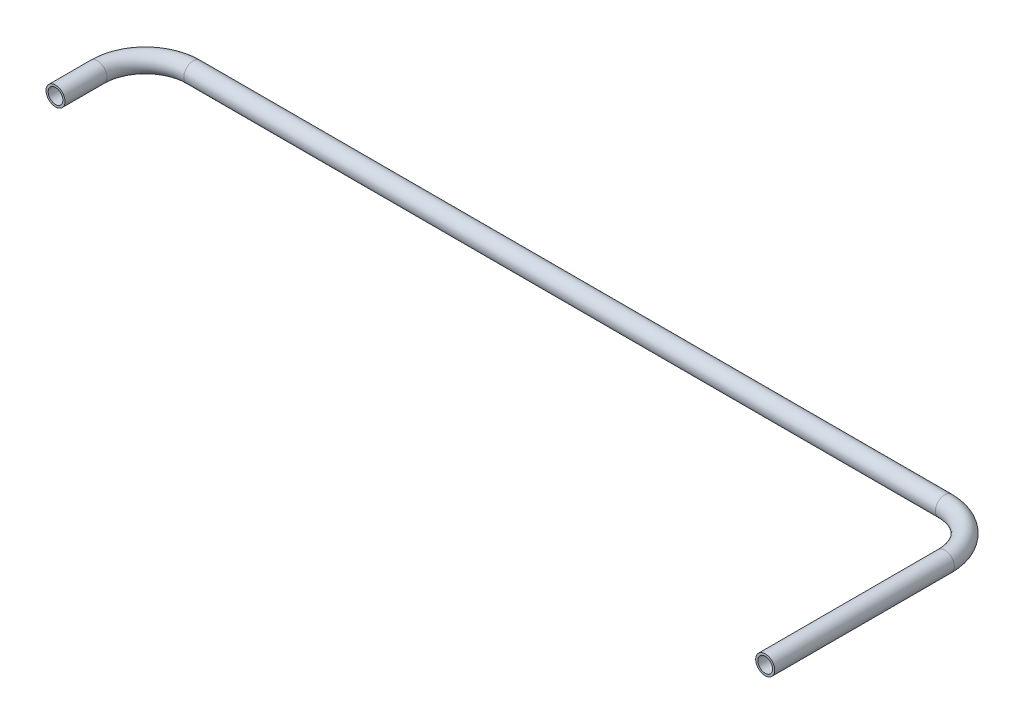
SolidWorks part; units mm, degrees
ref_plane "Front Plane" through (0, 0, 0) normal (0, 0, 1) x (1, 0, 0)
ref_plane "Top Plane" through (0, 0, 0) normal (0, 1, 0) x (1, 0, 0)
ref_plane "Right Plane" through (0, 0, 0) normal (1, 0, 0) x (0, 0, -1)
sketch "Sketch1" plane through (0, 0, 0) normal (0, 1, 0) x (1, 0, 0)
  line L0 (0, 0) -> (0, 14)
  line L1 (16, 30) -> (267, 30)
  line L2 (283, 14) -> (283, -46)
  arc A0 (267, 30) -> (283, 14) centre (267, 14) cw
  arc A1 (0, 14) -> (16, 30) centre (16, 14) cw
  dimension "D1" = 16
  dimension "D2" = 16
  dimension "D3" = 14
  dimension "D4" = 60
  dimension "D5" = 283
sketch "Sketch2" plane through (0, 0, 0) normal (0, 0, 1) x (1, 0, 0)
  circle A0 centre (0, 0) radius 3.175
  dimension "D1" = 6.35
sweep "Sweep-Thin1" add profiles "Sketch2" path "Sketch1" parameters "D1"=0.7112
